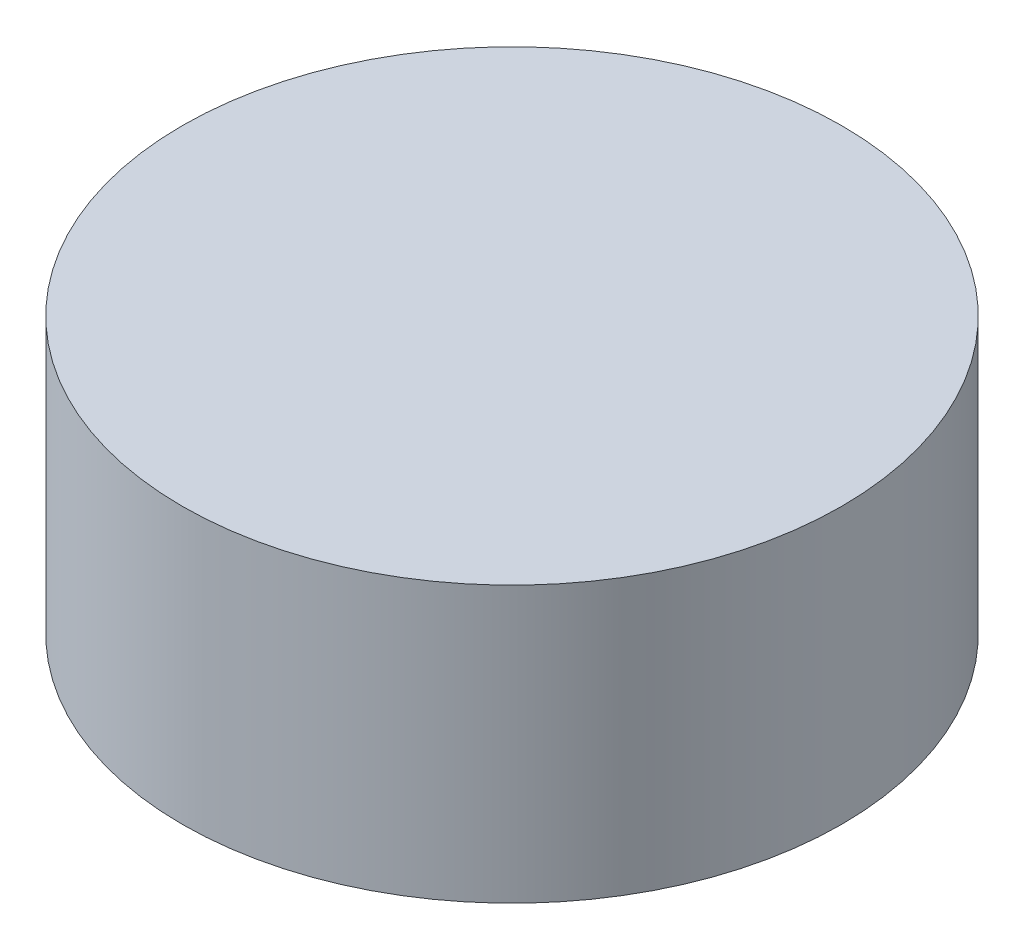
SolidWorks part; units mm, degrees
ref_plane "Front Plane" through (0, 0, 0) normal (0, 0, 1) x (1, 0, 0)
ref_plane "Top Plane" through (0, 0, 0) normal (0, 1, 0) x (1, 0, 0)
ref_plane "Right Plane" through (0, 0, 0) normal (1, 0, 0) x (0, 0, -1)
sketch "Sketch4" plane through (0, 0, 0) normal (0, 0, 1) x (1, 0, 0)
  line L1 (3.1743, 2.0493) -> (8.0578, 2.0493)
  line L2 (3.1743, 2.0493) -> (3.1743, -2.0307)
  line L3 (3.1743, -2.0307) -> (8.0578, -2.0307)
  line L4 (8.0578, 2.0493) -> (8.0578, -2.0307)
  dimension "D1" = 4.08
revolve "Revolve1" add sketch "Sketch4" angle 360 about L2
